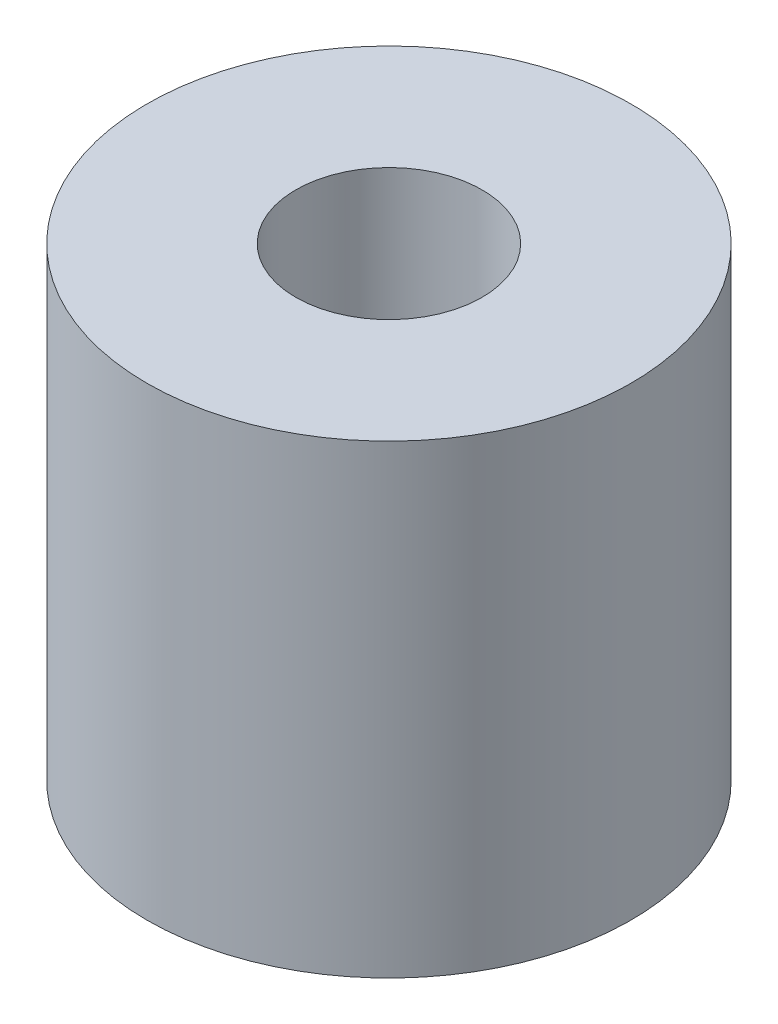
SolidWorks part; units mm, degrees
ref_plane "Front Plane" through (0, 0, 0) normal (0, 0, 1) x (1, 0, 0)
ref_plane "Top Plane" through (0, 0, 0) normal (0, 1, 0) x (1, 0, 0)
ref_plane "Right Plane" through (0, 0, 0) normal (1, 0, 0) x (0, 0, -1)
sketch "Sketch1" plane through (0, 0, 0) normal (0, 1, 0) x (1, 0, 0)
  circle A0 centre (0, 0) radius 5
  circle A1 centre (0, 0) radius 1.575
  dimension "D1" = 10
  dimension "D2" = 3.15
extrude "Boss-Extrude1" add sketch "Sketch1" along normal blind 9.607
sketch "Sketch2" plane through (0, 9.607, 0) normal (0, 1, 0) x (1, 0, 0)
  circle A0 centre (0, 0) radius 1.925
  circle M2 centre (0, 0) radius 1.575
  dimension "D1" = 3.85
extrude "Cut-Extrude1" cut sketch "Sketch2" against normal blind 4 contours M2 region at (-1.8706, 9.607, 0)
equation "\"bearing_21_OD\"= 21mm"
equation "\"pin_cirlce_diameter\"= 75mm"
equation "\"pin_diam\"= 6mm"
equation "\"gear_thickness\"= 4mm"
equation "\"ball_bearing_diam\"= 3.214mm"
equation "\"bearing_21_outer_clearance\"= 0.127mm'change this"
equation "\"bearing_15_OD\"= 15mm"
equation "\"bearing_15_outer_clearance\"= 0mm'change this"
equation "\"thrust_bearing_thickness\"= 5mm'measure this irl and change"
equation "\"D1@Boss-Extrude1\"=\"gear_thickness\"*2+0.5*\"ball_bearing_diam\""
